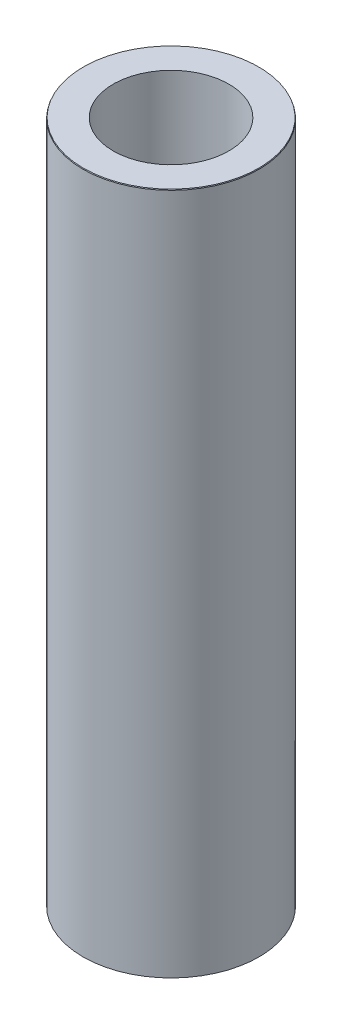
SolidWorks part; units mm, degrees
ref_plane "Front Plane" through (0, 0, 0) normal (0, 0, 1) x (1, 0, 0)
ref_plane "Top Plane" through (0, 0, 0) normal (0, 1, 0) x (1, 0, 0)
ref_plane "Right Plane" through (0, 0, 0) normal (1, 0, 0) x (0, 0, -1)
sketch "Sketch1" plane through (0, 0, 0) normal (0, 1, 0) x (1, 0, 0)
  circle A0 centre (0, 0) radius 22.5
  dimension "SHAFT_OD" = 45
extrude "Boss-Extrude1" add sketch "Sketch1" along normal blind 174.6695
sketch "Sketch2" plane through (0, 0, 0) normal (0, 1, 0) x (1, 0, 0)
  circle A0 centre (0, 0) radius 14.798
  dimension "BORE_D" = 29.5961
extrude "Cut-Extrude1" cut sketch "Sketch2" along normal through all
chamfer "Chamfer1" distance 0.2149 angle 20.858 2 edges at (0, 174.6695, 22.5) (0, 0, 22.5) first distance on face at (0, 174.6695, 22.5) first distance on face at (0, 0, 14.798)
